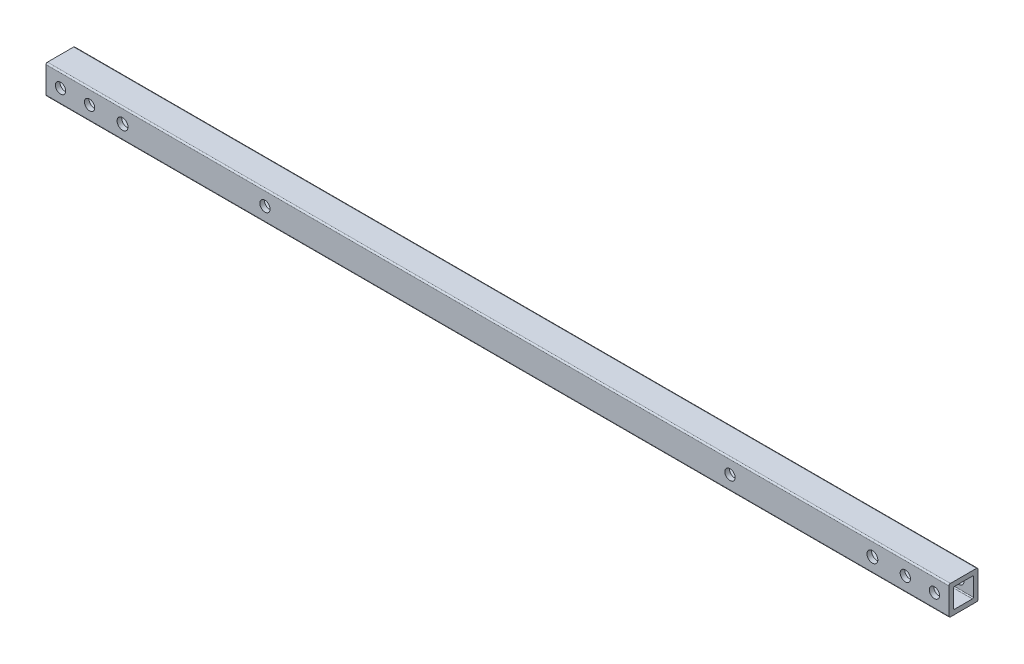
SolidWorks part; units mm, degrees
ref_plane "Front" through (0, 0, 0) normal (0, 0, 1) x (1, 0, 0)
ref_plane "Top" through (0, 0, 0) normal (0, 1, 0) x (1, 0, 0)
ref_plane "Right" through (0, 0, 0) normal (1, 0, 0) x (0, 0, -1)
sketch "Sketch1" plane through (0, 0, 0) normal (1, 0, 0) x (0, 0, -1)
  line L0 (-6.477, 0) -> (-9.525, 0) construction
  line L1 (8.5725, -9.525) -> (-8.5725, -9.525) construction
  line L2 (9.525, -8.5725) -> (9.525, 8.5725) construction
  line L3 (8.5725, 9.525) -> (-8.5725, 9.525) construction
  line L4 (-9.525, -8.5725) -> (-9.525, 8.5725) construction
  line L5 (9.525, -9.525) -> (-9.525, 9.525) construction
  line L6 (9.525, 9.525) -> (-9.525, -9.525) construction
  line L7 (5.8293, 6.477) -> (-5.8293, 6.477) construction
  line L8 (6.477, 5.8293) -> (6.477, -5.8293) construction
  line L9 (5.8293, -6.477) -> (-5.8293, -6.477) construction
  line L10 (-6.477, 5.8293) -> (-6.477, -5.8293) construction
  line L11 (6.477, 6.477) -> (-6.477, -6.477) construction
  line L12 (6.477, -6.477) -> (-6.477, 6.477) construction
  line L13 (0, -6.477) -> (0, -9.525) construction
  line L14 (6.477, -5.8293) -> (6.477, -9.525) construction
  line L15 (6.477, 0) -> (9.525, 0) construction
  line L16 (6.477, -9.525) -> (9.525, -9.525) construction
  arc A0 (-5.8293, -6.477) -> (-6.477, -5.8293) centre (-5.8293, -5.8293) cw construction
  arc A1 (6.477, -5.8293) -> (5.8293, -6.477) centre (5.8293, -5.8293) cw construction
  arc A2 (5.8293, 6.477) -> (6.477, 5.8293) centre (5.8293, 5.8293) cw construction
  arc A3 (-5.8293, 6.477) -> (-6.477, 5.8293) centre (-5.8293, 5.8293) ccw construction
  arc A4 (8.5725, -9.525) -> (9.525, -8.5725) centre (8.5725, -8.5725) ccw construction
  arc A5 (9.525, 8.5725) -> (8.5725, 9.525) centre (8.5725, 8.5725) ccw construction
  arc A6 (-8.5725, 9.525) -> (-9.525, 8.5725) centre (-8.5725, 8.5725) ccw construction
  arc A7 (-8.5725, -9.525) -> (-9.525, -8.5725) centre (-8.5725, -8.5725) cw construction
  point P0 (0, 0)
  point P6 (0, 0)
  dimension "D2" = 0.6477
  dimension "D3" = 0.9525
  dimension "Outside Width" = 19.05
  dimension "Ouside Height" = 19.05
  dimension "Inside Height" = 12.954
  dimension "Wall Thickness" = 3.048
sketch "Sketch2" plane through (0, 0, 0) normal (0, 0, 1) x (1, 0, 0)
  line L0 (-457.2, 0) -> (457.2, 0) construction
  point P3 (-441.198, 0)
  point P4 (441.198, 0)
  dimension "Length" = 914.4
  dimension "D1" = 16.002
  dimension "D2" = 16.002
sketch "Sketch4" plane through (0, 0, 0) normal (1, 0, 0) x (0, 0, -1)
  line L8 (9.525, -8.5725) -> (9.525, 8.5725)
  line L9 (8.5725, 9.525) -> (-8.5725, 9.525)
  line L10 (-9.525, -8.5725) -> (-9.525, 8.5725)
  line L11 (8.5725, -9.525) -> (-8.5725, -9.525)
  line L12 (6.477, 5.8293) -> (6.477, -5.8293)
  line L13 (5.8293, -6.477) -> (-5.8293, -6.477)
  line L14 (-6.477, 5.8293) -> (-6.477, -5.8293)
  line L15 (5.8293, 6.477) -> (-5.8293, 6.477)
  arc A8 (9.525, 8.5725) -> (8.5725, 9.525) centre (8.5725, 8.5725) ccw
  arc A9 (-8.5725, 9.525) -> (-9.525, 8.5725) centre (-8.5725, 8.5725) ccw
  arc A10 (-9.525, -8.5725) -> (-8.5725, -9.525) centre (-8.5725, -8.5725) ccw
  arc A11 (8.5725, -9.525) -> (9.525, -8.5725) centre (8.5725, -8.5725) ccw
  arc A12 (5.8293, -6.477) -> (6.477, -5.8293) centre (5.8293, -5.8293) ccw
  arc A13 (-6.477, -5.8293) -> (-5.8293, -6.477) centre (-5.8293, -5.8293) ccw
  arc A14 (-5.8293, 6.477) -> (-6.477, 5.8293) centre (-5.8293, 5.8293) ccw
  arc A15 (6.477, 5.8293) -> (5.8293, 6.477) centre (5.8293, 5.8293) ccw
extrude "Boss-Extrude1" add sketch "Sketch4" along normal mid plane 591.82
hole_wizard "1/4 Clearance Hole1" positions "Sketch5" profile "Sketch6" hole size "1/4" standard "ANSI Inch"
sketch "Sketch5" plane through (348.7325, 47.625, -9.525) normal (0, 0, -1) x (-1, 0, 0)
  line L0 (30.5975, -47.625) -> (81.3975, -47.625) construction
  line L1 (196.3325, 47.625) -> (196.3325, -47.625) construction
  point P0 (30.5975, -47.625)
  point P3 (62.3475, -47.625)
  point P5 (81.3975, -47.625)
  point P15 (196.3325, -47.625)
sketch "Sketch6" plane through (318.135, 0, -9.525) normal (1, 0, 0) x (0, 1, 0)
  line L0 (0, 0) -> (0, 21.0798)
  line L1 (0, 21.0798) -> (3.3782, 19.05)
  line L2 (3.3782, 19.05) -> (3.3782, 0)
  line L3 (3.3782, 0) -> (0, 0)
  line L4 (0, 21.0798) -> (-3.3782, 19.05) construction
  line L5 (0, -6.35) -> (0, 107.95) construction
  dimension "Hole Dia." = 6.7564
  dimension "Hole Depth" = 19.05
  dimension "Drill Angle" = 118
mirror "Mirror2" about plane through (0, 0, 0) normal (1, 0, 0) of "1/4 Clearance Hole1"
sketch "Sketch7" plane through (0, 0, 9.525) normal (0, 0, 1) x (1, 0, 0)
  line L0 (152.4, 0) -> (50152.4, 0) construction
  circle A0 centre (267.335, 0) radius 3.3782 construction
  circle A1 centre (-267.335, 0) radius 3.3782 construction
  point P0 (245.745, 0)
  point P8 (-245.745, 0)
  dimension "D2" = 21.59
  dimension "D1" = 21.59
hole_wizard "1/4 Clearance Hole2" positions "Sketch7" profile "Sketch8" hole size "1/4" standard "ANSI Inch" end condition through all
sketch "Sketch8" plane through (245.745, 0, 9.525) normal (1, 0, 0) x (0, -1, 0)
  line L0 (0, 0) -> (0, 19.05)
  line L1 (0, 19.05) -> (3.5712, 19.05)
  line L2 (3.5712, 19.05) -> (3.5712, 0)
  line L5 (3.5712, 0) -> (0, 0)
  line L11 (0, -6.35) -> (0, 107.95) construction
  dimension "Thru Hole Dia." = 7.1425
  dimension "Thru Hole Depth" = 19.05
equation "\"D3@Sketch1\"=\"Outside Width@Sketch1\"*.05"
equation "\"D2@Sketch1\" = \"Inside Height@Sketch1\" * .05"
equation "\"D1@Sketch2\"=\"Outside Width@Sketch1\"-\"Wall Thickness@Sketch1\""
equation "\"D2@Sketch2\"=\"D1@Sketch2\""
